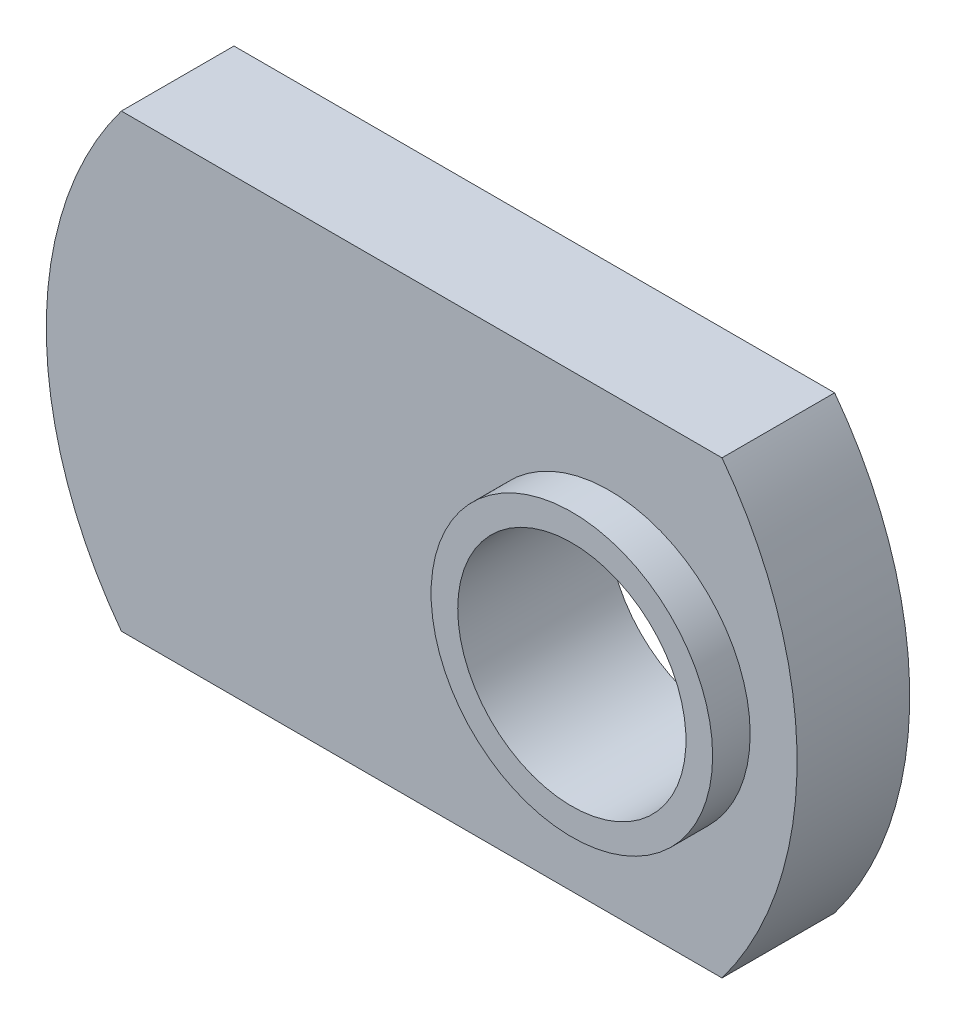
SolidWorks part; units mm, degrees
ref_plane "Front Plane" through (0, 0, 0) normal (0, 0, 1) x (1, 0, 0)
ref_plane "Top Plane" through (0, 0, 0) normal (0, 1, 0) x (1, 0, 0)
ref_plane "Right Plane" through (0, 0, 0) normal (1, 0, 0) x (0, 0, -1)
sketch "Sketch1" plane through (0, 0, 0) normal (0, 0, 1) x (1, 0, 0)
  line L0 (-6.35, 4.7625) -> (6.35, 4.7625)
  line L1 (-6.35, -4.7625) -> (6.35, -4.7625)
  line L2 (0, 0) -> (3.9688, 0) construction
  line L3 (3.9688, 0) -> (7.9375, 0) construction
  arc A0 (6.35, -4.7625) -> (6.35, 4.7625) centre (0, 0) ccw
  arc A2 (-6.35, 4.7625) -> (-6.35, -4.7625) centre (0, 0) ccw
  circle A3 centre (3.9688, 0) radius 2.413
  dimension "D1" = 4.826
  dimension "width" = 9.525
extrude "Extrude1" add sketch "Sketch1" along normal blind 2.3813
sketch "Sketch2" plane through (0, 0, 2.3813) normal (0, 0, 1) x (1, 0, 0)
  circle A0 centre (3.9688, 0) radius 2.9766
  circle A1 centre (3.9688, 0) radius 2.413
  circle A2 centre (3.9688, 0) radius 2.413 construction
extrude "Extrude2" add sketch "Sketch2" along normal blind 0.7937
sketch "Sketch3" plane through (0, 0, 0) normal (0, 0, -1) x (-1, 0, 0)
  circle A1 centre (-3.9688, 0) radius 2.413
  circle A2 centre (-3.9688, 0) radius 2.413 construction
curve "Helix/Spiral1" pitch 0.7937 height 7.1437 turns 9 parameters "pitch"=0.7937
sketch "Sketch4" [suppressed] plane through (0, 0, 0) normal (0, 1, 0) x (1, 0, 0)
  line L0 (1.5557, 0.6945) -> (1.5557, 0)
  line L1 (1.5557, 0) -> (2.0713, 0.2977)
  line L2 (2.0713, 0.2977) -> (2.0713, 0.3969)
  line L3 (2.0713, 0.3969) -> (1.5557, 0.6945)
  line L4 (2.0713, 0.3473) -> (1.5557, 0.3473) construction
  line L5 (1.8135, 0.1488) -> (1.8135, 0.5457) construction
  dimension "D1" = 0.0992
  dimension "D2" = 0.3969
  dimension "D3" = 60
sweep "Sweep1" [suppressed] add profiles "Sketch4" path "Helix/Spiral1"
sketch "Sketch5" [suppressed] plane through (0, 0, 0) normal (0, 0, -1) x (-1, 0, 0)
  line L2 (-6.35, -4.7625) -> (6.35, -4.7625)
  line L3 (-6.35, -4.7625) -> (6.35, -4.7625)
  line L4 (6.35, 4.7625) -> (-6.35, 4.7625)
  line L5 (6.35, 4.7625) -> (-6.35, 4.7625)
  arc A1 (-6.35, 4.7625) -> (-6.35, -4.7625) centre (0, 0) ccw
  arc A2 (-6.35, 4.7625) -> (-6.35, -4.7625) centre (0, 0) ccw
  arc A4 (6.35, -4.7625) -> (6.35, 4.7625) centre (0, 0) ccw
  arc A5 (6.35, -4.7625) -> (6.35, 4.7625) centre (0, 0) ccw
  dimension "D1" = 0
extrude "Cut-Extrude1" [suppressed] cut sketch "Sketch5" along normal through all
sketch "Sketch6" [suppressed] plane through (0, 0, 0) normal (0, 0, -1) x (-1, 0, 0)
  circle A1 centre (-3.9688, 0) radius 2.413
  circle A2 centre (-3.9688, 0) radius 2.413 construction
extrude "Cut-Extrude2" [suppressed] cut sketch "Sketch6" against normal through all draft 45
sketch "Sketch7" [suppressed] plane through (0, 0, 3.175) normal (0, 0, 1) x (1, 0, 0)
  circle A1 centre (3.9688, 0) radius 2.9766
  circle A2 centre (3.9688, 0) radius 2.9766
  dimension "D1" = 0
extrude "Cut-Extrude3" [suppressed] cut sketch "Sketch7" along normal through all
sketch "Sketch8" [suppressed] plane through (0, 0, 3.175) normal (0, 0, 1) x (1, 0, 0)
  circle A1 centre (3.9688, 0) radius 2.413
  circle A2 centre (3.9688, 0) radius 2.413 construction
extrude "Cut-Extrude4" [suppressed] cut sketch "Sketch8" against normal through all draft 45
ref_axis "Center Axis 1" [suppressed] through (3.9688, 0, 0.5156) along (0, 0, 1)
ref_plane "Contact Plane 1" through (0, 0, 2.3813) normal (0, 0, 1) x (1, 0, 0)
ref_plane "Contact Plane 2" through (0, 0, 0) normal (0, 0, -1) x (-1, 0, 0)
equation "\"D1@Sketch1\" = \"OD@Sketch2\""
equation "\"D3@Helix/Spiral1\" = \"height@Extrude2\"+.250"
equation "\"D1@Sketch4\" = \"pitch@Helix/Spiral1\"*.125"
equation "\"D2@Sketch4\" = \"pitch@Helix/Spiral1\"*.5"
